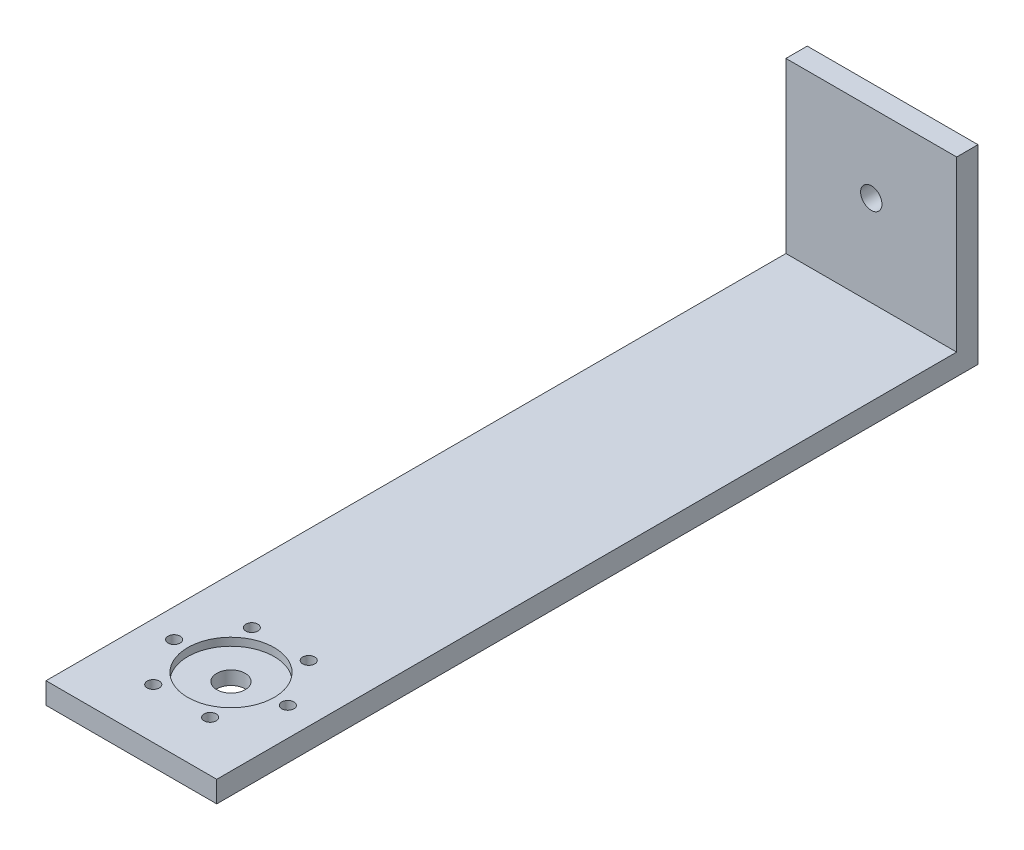
SolidWorks part; units mm, degrees
material "6061-T6 (SS)"
ref_plane "Front Plane" through (0, 0, 0) normal (0, 0, 1) x (1, 0, 0)
ref_plane "Top Plane" through (0, 0, 0) normal (0, 1, 0) x (1, 0, 0)
ref_plane "Right Plane" through (0, 0, 0) normal (1, 0, 0) x (0, 0, -1)
ref_plane "PL_Forearm_Plate_base" through (0, -31.5, 0) normal (0, 1, 0) x (1, 0, 0)
sketch "SK_Forearm_Plate" plane through (0, -31.5, 0) normal (0, 1, 0) x (1, 0, 0)
  line L0 (-24, -28) -> (24, -28)
  line L1 (24, -28) -> (24, 180)
  line L2 (24, 180) -> (-24, 180)
  line L3 (-24, 180) -> (-24, -28)
  circle A0 centre (16, 0) radius 1.7
  circle A1 centre (8, 13.8564) radius 1.7
  circle A2 centre (-8, 13.8564) radius 1.7
  circle A3 centre (-16, 0) radius 1.7
  circle A4 centre (-8, -13.8564) radius 1.7
  circle A5 centre (8, -13.8564) radius 1.7
  circle A6 centre (0, 0) radius 4
  dimension "D9_SK_Forearm_Plate" = 3.4
  dimension "D11_SK_Forearm_Plate" = 3.4
  dimension "D14_SK_Forearm_Plate" = 3.4
  dimension "D17_SK_Forearm_Plate" = 3.4
  dimension "D19_SK_Forearm_Plate" = 3.4
  dimension "D22_SK_Forearm_Plate" = 3.4
  dimension "D25_SK_Forearm_Plate" = 8
  dimension "P1" = 24
  dimension "P2" = 28
  dimension "P3" = 24
  dimension "P4" = 28
  dimension "P5" = 24
  dimension "P6" = 180
  dimension "P7" = 24
  dimension "P8" = 180
  dimension "P10" = 16
  dimension "P12" = 8
  dimension "P13" = 13.8564
  dimension "P15" = 8
  dimension "P16" = 13.8564
  dimension "P18" = 16
  dimension "P20" = 8
  dimension "P21" = 13.8564
  dimension "P23" = 8
  dimension "P24" = 13.8564
extrude "Forearm_Plate" add sketch "SK_Forearm_Plate" along normal blind 6
ref_plane "PL_Elbow_Pilot_Recess_base" through (0, -25.5, 0) normal (0, 1, 0) x (1, 0, 0)
sketch "SK_Elbow_Pilot_Recess" plane through (0, -25.5, 0) normal (0, 1, 0) x (1, 0, 0)
  circle A0 centre (0, 0) radius 12.15
  dimension "D1_SK_Elbow_Pilot_Recess" = 24.3
extrude "Elbow_Pilot_Recess" cut sketch "SK_Elbow_Pilot_Recess" against normal blind 2.2
ref_plane "PL_Hand_Plate_base" through (0, 0, -186) normal (0, 0, 1) x (1, 0, 0)
sketch "SK_Hand_Plate" plane through (0, 0, -186) normal (0, 0, 1) x (1, 0, 0)
  line L0 (-24, 22) -> (24, 22)
  line L1 (24, 22) -> (24, -31.5)
  line L2 (24, -31.5) -> (-24, -31.5)
  line L3 (-24, -31.5) -> (-24, 22)
  circle A0 centre (0, 0) radius 3
  dimension "D9_SK_Hand_Plate" = 6
  dimension "P1" = 24
  dimension "P2" = 22
  dimension "P3" = 24
  dimension "P4" = 22
  dimension "P5" = 24
  dimension "P6" = 31.5
  dimension "P7" = 24
  dimension "P8" = 31.5
extrude "Hand_Plate" add sketch "SK_Hand_Plate" along normal blind 6
equation "\"Forearm_length\"= 180"
